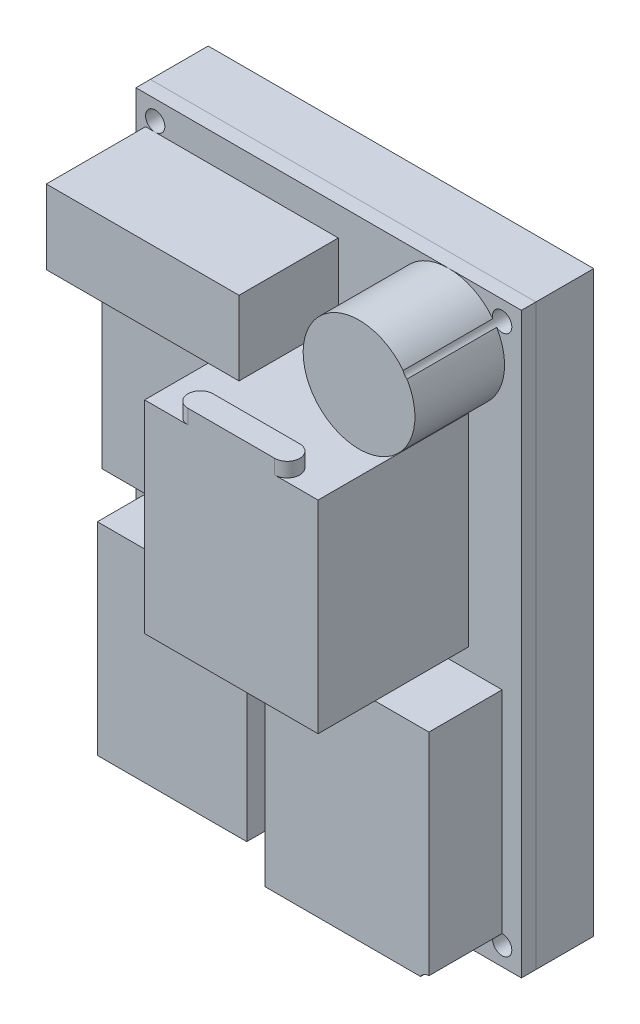
SolidWorks part; units mm, degrees
ref_plane "Front Plane" through (0, 0, 0) normal (1, 0, 0) x (0, 1, 0)
ref_plane "Top Plane" through (0, 0, 0) normal (0, 0, 1) x (0, 1, 0)
ref_plane "Right Plane" through (0, 0, 0) normal (0, 1, 0) x (-1, 0, 0)
sketch "Sketch1" plane through (0, 0, 0) normal (0, 0, 1) x (0, 1, 0)
  line L0 (-30, 20) -> (30, -20) construction
  line L1 (-30, 20) -> (30, 20)
  line L2 (-30, 20) -> (-30, -20)
  line L3 (-30, -20) -> (30, -20)
  line L4 (30, 20) -> (30, -20)
  line L5 (0, -1000) -> (0, 49000) construction
  line L6 (-1000, 0) -> (49000, 0) construction
  circle A0 centre (28, 18) radius 1
  circle A2 centre (-28, 18) radius 1
  circle A3 centre (-28, -18) radius 1
  circle A4 centre (28, -18) radius 1
  point P4 (0, 0)
  dimension "D3" = 2
  dimension "D1" = 40
  dimension "D2" = 60
  dimension "D4" = 2
  dimension "D5" = 2
extrude "Boss-Extrude1" add sketch "Sketch1" along normal blind 1.5
sketch "Sketch2" plane through (0, 0, 1.5) normal (0, 0, 1) x (1, 0, 0)
  line L0 (-20, -30) -> (20, -30) construction
  line L1 (-18, -26) -> (-2.5, -26)
  line L2 (-18, -26) -> (-18, -5)
  line L3 (-18, -5) -> (-2.5, -5)
  line L4 (-2.5, -26) -> (-2.5, -5)
  line L5 (1, -27.5) -> (18, -27.5)
  line L6 (1, -27.5) -> (1, -5.1)
  line L7 (1, -5.1) -> (18, -5.1)
  line L8 (18, -27.5) -> (18, -5.1)
  line L9 (-3.5, -3) -> (14.5, -3)
  line L10 (-3.5, -3) -> (-3.5, 18)
  line L11 (-3.5, 18) -> (14.5, 18)
  line L12 (14.5, -3) -> (14.5, 18)
  line L13 (-19, 27) -> (1, 27)
  line L14 (-19, 27) -> (-19, 19.3)
  line L15 (-19, 19.3) -> (1, 19.3)
  line L16 (1, 27) -> (1, 19.3)
  line L17 (-17.5, 0) -> (-6.5, 0)
  line L18 (-17.5, 0) -> (-17.5, 15)
  line L19 (-17.5, 15) -> (-6.5, 15)
  line L20 (-6.5, 0) -> (-6.5, 15)
  line L21 (-20, 30) -> (-20, -30) construction
  line L22 (20, -30) -> (20, 30) construction
  line L23 (20, 30) -> (-20, 30) construction
  circle A0 centre (12.45, 24.2) radius 5.8
  circle M18 centre (18, -28) radius 1
  circle M25 centre (18, 28) radius 1
  dimension "D21" = 11.6
  dimension "D22" = 7.55
  dimension "D1" = 4
  dimension "D2" = 2
  dimension "D3" = 21
  dimension "D4" = 15.5
  dimension "D5" = 17
  dimension "D6" = 22.4
  dimension "D7" = 2.5
  dimension "D8" = 2
  dimension "D9" = 5.5
  dimension "D10" = 12
  dimension "D11" = 18
  dimension "D12" = 21
  dimension "D13" = 15
  dimension "D14" = 11
  dimension "D15" = 2.5
  dimension "D16" = 15
  dimension "D17" = 1
  dimension "D18" = 3
  dimension "D19" = 7.7
  dimension "D20" = 20
extrude "Boss-Extrude2" add sketch "Sketch2" along normal blind 6 contours L1 L4 L3 L2 | L17 L20 L19 L18 region at (-10.25, -15.5, 1.5) region at (-12, 7.5, 1.5)
extrude "Boss-Extrude3" add sketch "Sketch2<3>" along normal blind 7.6 contours L8 L7 L6 L5 M18 region at (9.4934, -16.2911, 1.5)
sketch "Sketch2<3>" plane through (0, 0, 1.5) normal (0, 0, 1) x (1, 0, 0) same geometry as "Sketch2"
extrude "Boss-Extrude4" add sketch "Sketch2<4>" along normal blind 15.6 contours L9 L12 L11 L10 region at (5.5, 7.5, 1.5)
sketch "Sketch2<4>" plane through (0, 0, 1.5) normal (0, 0, 1) x (1, 0, 0) same geometry as "Sketch2"
extrude "Boss-Extrude5" add sketch "Sketch2<5>" along normal blind 9.3 contours A0 M25 region at (12.4484, 24.1989, 1.5)
sketch "Sketch2<5>" plane through (0, 0, 1.5) normal (0, 0, 1) x (1, 0, 0) same geometry as "Sketch2"
extrude "Boss-Extrude6" add sketch "Sketch2<6>" along normal blind 10.3 contours L16 L13 L14 L15 region at (-9, 23.15, 1.5)
sketch "Sketch2<6>" plane through (0, 0, 1.5) normal (0, 0, 1) x (1, 0, 0) same geometry as "Sketch2"
extrude "Boss-Extrude7" add sketch "Sketch1<3>" against normal blind 6 separate body
sketch "Sketch1<3>" plane through (0, 0, 0) normal (0, 0, 1) x (0, 1, 0) same geometry as "Sketch1"
sketch "Sketch4" plane through (0, 18, 0) normal (0, 1, 0) x (-1, 0, 0)
  line L0 (-10, 15.8) -> (-1, 15.8) construction
  line L1 (-10, 17.1) -> (-1, 17.1)
  line L2 (-10, 14.5) -> (-1, 14.5)
  line L4 (3.5, 17.1) -> (-14.5, 17.1) construction
  line L5 (-10, 15.8) -> (-14.5, 15.8) construction
  line L6 (-14.5, 17.1) -> (-14.5, 1.5) construction
  line L7 (-1, 15.8) -> (3.5, 15.8) construction
  line L8 (3.5, 17.1) -> (3.5, 1.5) construction
  arc A0 (-10, 17.1) -> (-10, 14.5) centre (-10, 15.8) ccw
  arc A1 (-1, 14.5) -> (-1, 17.1) centre (-1, 15.8) ccw
  point P2 (-5.5, 15.8)
  dimension "D1" = 2.6
  dimension "D2" = 9
extrude "Boss-Extrude8" add sketch "Sketch4" along normal blind 1.5
